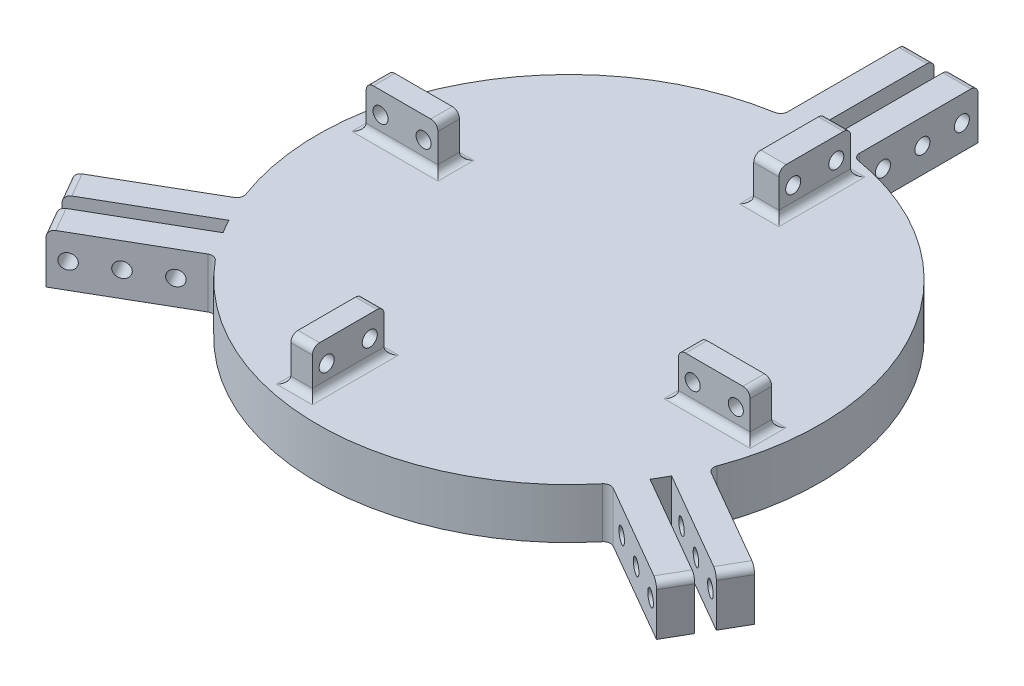
SolidWorks part; units mm, degrees
ref_plane "Front Plane" through (0, 0, 0) normal (0, 0, 1) x (1, 0, 0)
ref_plane "Top Plane" through (0, 0, 0) normal (0, 1, 0) x (1, 0, 0)
ref_plane "Right Plane" through (0, 0, 0) normal (1, 0, 0) x (0, 0, -1)
sketch "Sketch1" plane through (0, 0, 0) normal (0, 1, 0) x (1, 0, 0)
  circle A0 centre (0, 0) radius 35
  dimension "D1" = 70
extrude "Boss-Extrude1" add sketch "Sketch1" along normal blind 7
sketch "Sketch2" plane through (0, 7, 0) normal (0, 1, 0) x (1, 0, 0)
  line L0 (0, 3.75) -> (0, -3.75) construction
  line L1 (-3.75, 0) -> (3.75, 0) construction
  line L2 (-3.75, 22) -> (-3.75, -22) construction
  line L19 (3.75, 22) -> (3.75, -22) construction
  line L24 (-22, 3.75) -> (22, 3.75) construction
  line L25 (-22, -3.75) -> (22, -3.75) construction
  line L27 (3.75, 22) -> (7.25, 22)
  line L28 (3.75, 22) -> (3.75, 32)
  line L29 (3.75, 32) -> (7.25, 32)
  line L30 (7.25, 22) -> (7.25, 32)
  line L35 (-22, 3.75) -> (-32, 3.75)
  line L36 (-22, 3.75) -> (-22, 6.75)
  line L37 (-22, 6.75) -> (-32, 6.75)
  line L38 (-32, 3.75) -> (-32, 6.75)
  line L59 (-3.75, -22) -> (-6.75, -22)
  line L60 (-3.75, -22) -> (-3.75, -32)
  line L61 (-3.75, -32) -> (-6.75, -32)
  line L62 (-6.75, -22) -> (-6.75, -32)
  line L63 (22, -3.75) -> (32, -3.75)
  line L64 (22, -3.75) -> (22, -6.75)
  line L65 (22, -6.75) -> (32, -6.75)
  line L66 (32, -3.75) -> (32, -6.75)
  point P5 (0, 0)
  point P6 (0, 0)
  dimension "D1" = 7.5
  dimension "D2" = 7.5
  dimension "D3" = 10
  dimension "D4" = 3.5
  dimension "D5" = 44
  dimension "D6" = 3
extrude "Boss-Extrude2" add sketch "Sketch2" along normal blind 6
sketch "Sketch3" plane through (0, 0, 0) normal (0, 1, 0) x (1, 0, 0)
  line L0 (-5, 30) -> (5, 30) construction
  line L5 (5, 30) -> (1.1, 30)
  line L6 (5, 30) -> (5, 52)
  line L7 (5, 52) -> (1.1, 52)
  line L8 (1.1, 30) -> (1.1, 52)
  line L9 (-5, 30) -> (-1.1, 30)
  line L10 (-5, 30) -> (-5, 52)
  line L11 (-5, 52) -> (-1.1, 52)
  line L12 (-1.1, 30) -> (-1.1, 52)
  line L13 (0, 30) -> (0, 0) construction
  line L14 (23.4808, -19.3301) -> (25.4308, -15.9526)
  line L15 (23.4808, -19.3301) -> (42.5333, -30.3301)
  line L16 (42.5333, -30.3301) -> (44.4833, -26.9526)
  line L17 (25.4308, -15.9526) -> (44.4833, -26.9526)
  line L18 (28.4808, -10.6699) -> (26.5308, -14.0474)
  line L19 (28.4808, -10.6699) -> (47.5333, -21.6699)
  line L20 (47.5333, -21.6699) -> (45.5833, -25.0474)
  line L21 (26.5308, -14.0474) -> (45.5833, -25.0474)
  line L22 (28.4808, -10.6699) -> (23.4808, -19.3301) construction
  line L23 (25.9808, -15) -> (0, 0) construction
  line L24 (-28.4808, -10.6699) -> (-26.5308, -14.0474)
  line L25 (-28.4808, -10.6699) -> (-47.5333, -21.6699)
  line L26 (-47.5333, -21.6699) -> (-45.5833, -25.0474)
  line L27 (-26.5308, -14.0474) -> (-45.5833, -25.0474)
  line L28 (-23.4808, -19.3301) -> (-25.4308, -15.9526)
  line L29 (-23.4808, -19.3301) -> (-42.5333, -30.3301)
  line L30 (-42.5333, -30.3301) -> (-44.4833, -26.9526)
  line L31 (-25.4308, -15.9526) -> (-44.4833, -26.9526)
  line L32 (-23.4808, -19.3301) -> (-28.4808, -10.6699) construction
  line L33 (-25.9808, -15) -> (0, 0) construction
  point P31 (0, 0)
  dimension "D1" = 3.9
  dimension "D2" = 2.2
  dimension "D3" = 30
  dimension "D5" = 22
  dimension "D4" = 3
extrude "Boss-Extrude3" add sketch "Sketch3" along normal up to surface (7 mm away) up to face at (0, 7, 35)
ref_axis "Axis1" through (0, 13.65, 0) along (0, -1, 0)
sketch "Sketch4" plane through (5, 0, 0) normal (1, 0, 0) x (0, 0, -1)
  line L0 (49.75, 3.5) -> (52, 3.5) construction
  line L3 (52, 7) -> (52, 0) construction
  line L4 (44.25, 3.5) -> (38.75, 3.5) construction
  line L5 (44.25, 3.5) -> (49.75, 3.5) construction
  circle A0 centre (49.75, 3.5) radius 1.05
  circle A1 centre (44.25, 3.5) radius 1.05
  circle A2 centre (38.75, 3.5) radius 1.05
  dimension "D1" = 2.25
  dimension "D2" = 2.1
  dimension "D4" = 5.5
extrude "Cut-Extrude1" cut sketch "Sketch4" against normal blind 10
pattern_circular "CirPattern1" count 3 over 360 about axis through (0, 13.65, 0) along (0, -1, 0) of "Cut-Extrude1"
sketch "Sketch5" plane through (3.75, 0, 0) normal (-1, 0, 0) x (0, 0, 1)
  line L0 (-27, 13) -> (-27, 7) construction
  line L7 (-27, 10) -> (-30, 10) construction
  line L8 (-27, 10) -> (-24, 10) construction
  circle A0 centre (-30, 10) radius 1.05
  circle A1 centre (-24, 10) radius 1.05
  circle A3 centre (-44.25, 3.5) radius 1.05 construction
  dimension "D1" = 6
extrude "Cut-Extrude2" cut sketch "Sketch5" against normal through all
pattern_circular "CirPattern2" count 4 over 360 about axis through (0, 13.65, 0) along (0, -1, 0) of "Cut-Extrude2"
ref_plane "Plane1" through (0, 0, -3.625) normal (0, 0, 1) x (1, 0, 0)
sketch "Sketch6" plane through (0, 0, -3.625) normal (0, 0, 1) x (1, 0, 0)
  circle A0 centre (-30, 10) radius 1.025
  circle A1 centre (30, 10) radius 1.025
ref_plane "Plane2" through (3.625, 0, 0) normal (-1, 0, 0) x (0, 0, 1)
sketch "Sketch7" plane through (3.625, 0, 0) normal (-1, 0, 0) x (0, 0, 1)
  circle A0 centre (-30, 10) radius 1.025
  circle A1 centre (30, 10) radius 1.025
  circle A2 centre (-24, 10) radius 1.025
  circle A3 centre (24, 10) radius 1.025
fillet "Fillet1" radius 1 36 edges at (-32, 7, -5.25) (-22, 7, -5.25) (5.5, 7, -22) (5.5, 7, -32) (3.05, 7, -52) (-3.05, 7, -52) (-43.5083, 7, 28.6414) (-46.5583, 7, 23.3586) (43.5083, 7, 28.6414) (46.5583, 7, 23.3586) (5.5, 13, -22) (5.5, 13, -32) (-32, 13, -5.25) (-22, 13, -5.25) (32, 13, 5.25) (22, 13, 5.25) (-5.25, 13, 22) (-5.25, 13, 32) (27, 7, 6.75) (22, 7, 5.25) (32, 7, 5.25) (7.25, 7, -27) (-27, 7, -6.75) (-6.75, 7, 27) (-5.25, 7, 22) (-5.25, 7, 32) (32.5, 3.5, 12.9904) (27.5, 3.5, 21.6506) (-32.5, 3.5, 12.9904) (-27.5, 3.5, 21.6506) (-5, 3.5, -34.641) (5, 3.5, -34.641) (3.75, 7, -27) (27, 7, 3.75) (-27, 7, -3.75) (-3.75, 7, 27)
equation "\"D2@Sketch2\"=\"D1@Sketch2\""
